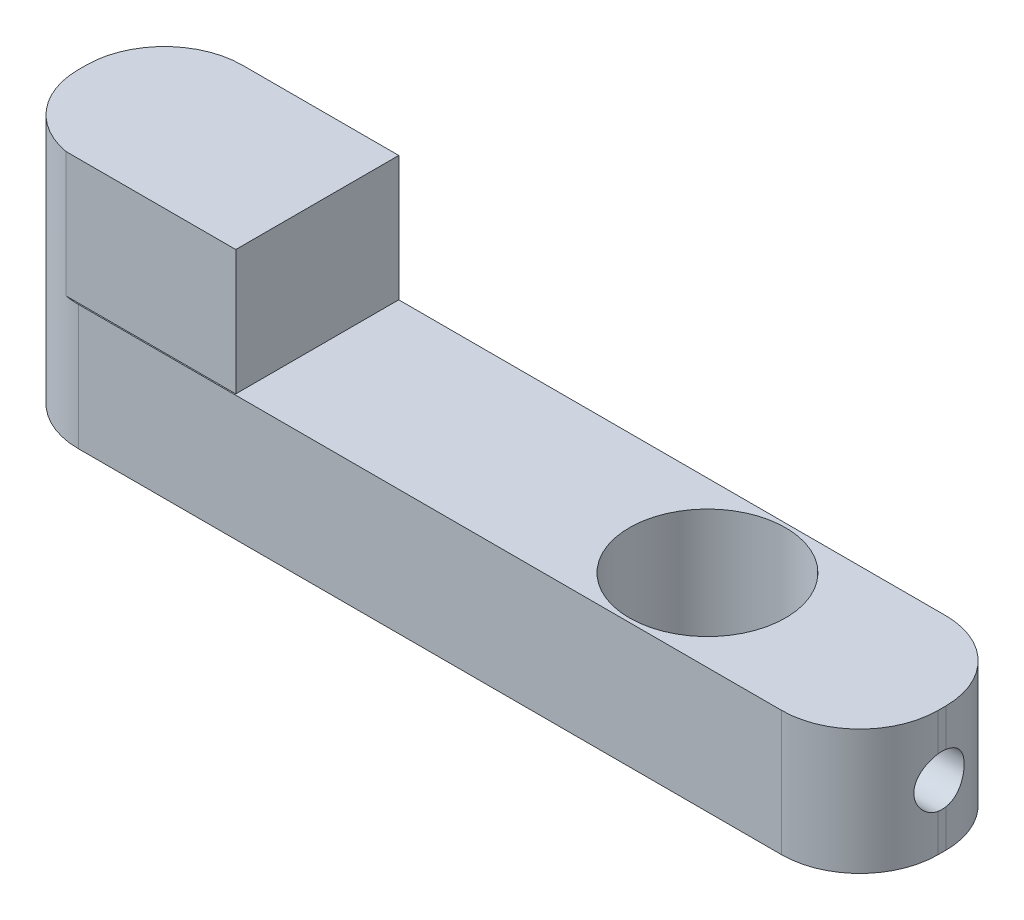
SolidWorks part; units mm, degrees
ref_plane "Front Plane" through (0, 0, 0) normal (0, 0, 1) x (1, 0, 0)
ref_plane "Top Plane" through (0, 0, 0) normal (0, 1, 0) x (1, 0, 0)
ref_plane "Right Plane" through (0, 0, 0) normal (1, 0, 0) x (0, 0, -1)
sketch "Sketch1" plane through (0, 0, 0) normal (0, 1, 0) x (1, 0, 0)
  line L0 (0, 0) -> (-275, 0) construction
  line L1 (-275, 52.5) -> (275, 52.5)
  line L2 (-275, 52.5) -> (-275, -52.5)
  line L3 (-275, -52.5) -> (275, -52.5)
  line L4 (275, 52.5) -> (275, -52.5)
  line L5 (-275, 52.5) -> (275, -52.5) construction
  line L6 (-275, -52.5) -> (275, 52.5) construction
  line L7 (0, 0) -> (275, 0) construction
  circle A0 centre (-220, 0) radius 50
  circle A1 centre (125, 0) radius 50
  point P0 (0, 0)
  dimension "D4" = 100
  dimension "D6" = 100
  dimension "D1" = 550
  dimension "D2" = 105
  dimension "D3" = 55
  dimension "D5" = 150
extrude "Boss-Extrude2" add sketch "Sketch1" along normal blind 80
fillet "Fillet4" radius 50 1 edges at (275, 40, 52.5) type face fillet first side face at (0, 40, 52.5) second side face at (275, 40, 0)
fillet "Fillet5" radius 50 1 edges at (275, 40, -52.5) type face fillet first side face at (275, 40, -25) second side face at (0, 40, -52.5)
sketch "Sketch10" plane through (275, 0, 0) normal (1, 0, 0) x (0, 0, -1)
  circle A0 centre (0, 40) radius 16.1
  dimension "D1" = 32.2
extrude "Cut-Extrude2" cut sketch "Sketch10" against normal blind 150 contours A0
sketch "Sketch11" plane through (0, 80, 0) normal (0, 1, 0) x (1, 0, 0)
  line L0 (-275, 52.5) -> (-125, 52.5)
  line L1 (-275, 52.5) -> (-275, -51.7681)
  line L2 (-125, 52.5) -> (-125, -51.7681)
  line L3 (-275, -51.7681) -> (-125, -51.7681)
  line L4 (225, 52.5) -> (-275, 52.5) construction
  dimension "D1" = 150
extrude "Boss-Extrude3" add sketch "Sketch11" along normal blind 80
sketch "Sketch12" plane through (0, 80, 0) normal (0, -1, 0) x (1, 0, 0)
  circle A0 centre (-220, 0) radius 5
  dimension "D1" = 10
extrude "Boss-Extrude4" add sketch "Sketch12" along normal blind 100
fillet "Fillet8" radius 50 2 edges at (-275, 40, 52.5) (-275, 120, 51.7681) type face fillet first side face at (-275, 80, 17.256) second side face at (-25, 40, 52.5) second side face at (-200, 120, 51.7681)
fillet "Fillet9" radius 50 1 edges at (-275, 80, -52.5) type face fillet first side face at (-58.3333, 80, -52.5) second side face at (-275, 80, -25)
